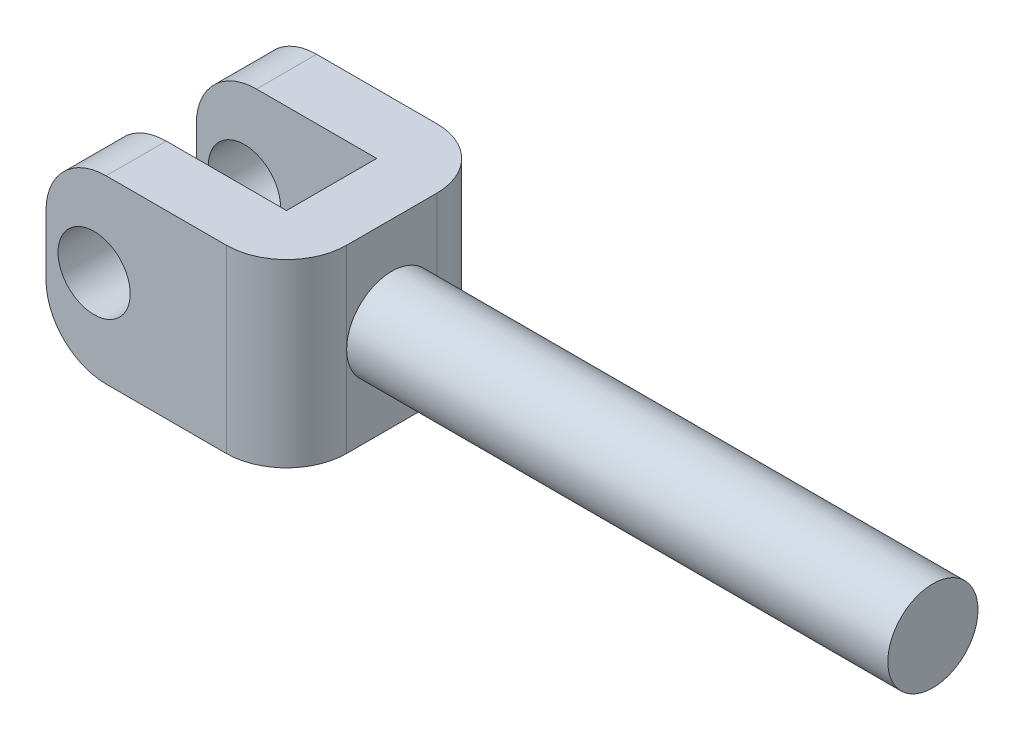
SolidWorks part; units mm, degrees
ref_plane "Front Plane" through (0, 0, 0) normal (0, 0, 1) x (1, 0, 0)
ref_plane "Top Plane" through (0, 0, 0) normal (0, 1, 0) x (1, 0, 0)
ref_plane "Right Plane" through (0, 0, 0) normal (1, 0, 0) x (0, 0, -1)
sketch "Sketch1" plane through (0, 0, 0) normal (1, 0, 0) x (0, 0, -1)
  circle A0 centre (0, 0) radius 0.75
  dimension "D1" = 1.5
extrude "Boss-Extrude1" add sketch "Sketch1" along normal blind 10
sketch "Sketch2" plane through (0, 0, 0) normal (0, 1, 0) x (1, 0, 0)
  line L0 (1, 1.75) -> (1, -1.75)
  line L2 (0, 0.75) -> (0, -0.75)
  line L5 (1, -1.75) -> (-3, -1.75)
  line L6 (-3, 1.75) -> (-3, 0.75)
  line L7 (1, 1.75) -> (-3, 1.75)
  line L8 (0, 0.75) -> (-3, 0.75)
  line L10 (-3, -0.75) -> (0, -0.75)
  line L11 (-3, -0.75) -> (-3, -1.75)
  line L13 (-3, 1.75) -> (-3, -1.75) construction
  line L14 (-2, 0.75) -> (-2, -0.75) construction
  line L15 (0, 0.75) -> (-2, 0.75) construction
  line L16 (0, -0.75) -> (-2, -0.75) construction
  dimension "D1" = 4
  dimension "D2" = 1
extrude "Boss-Extrude2" add sketch "Sketch2" along normal blind 1.5 and the other way blind 1.5
fillet "Fillet1" radius 1 6 edges at (-3, 1.5, -1.25) (-3, -1.5, -1.25) (-3, -1.5, 1.25) (-3, 1.5, 1.25) (1, 0, -1.75) (1, 0, 1.75)
sketch "Sketch3" plane through (0, 0, -1.75) normal (0, 0, -1) x (-1, 0, 0)
  line L0 (0, -1.5) -> (2, -1.5) construction
  line L2 (0, 1.5) -> (0, -1.5) construction
  circle A0 centre (2.2, 0) radius 0.6
  dimension "D1" = 1.2
  dimension "D2" = 1.5
  dimension "D3" = 2.2
extrude "Cut-Extrude1" cut sketch "Sketch3" against normal blind 5
